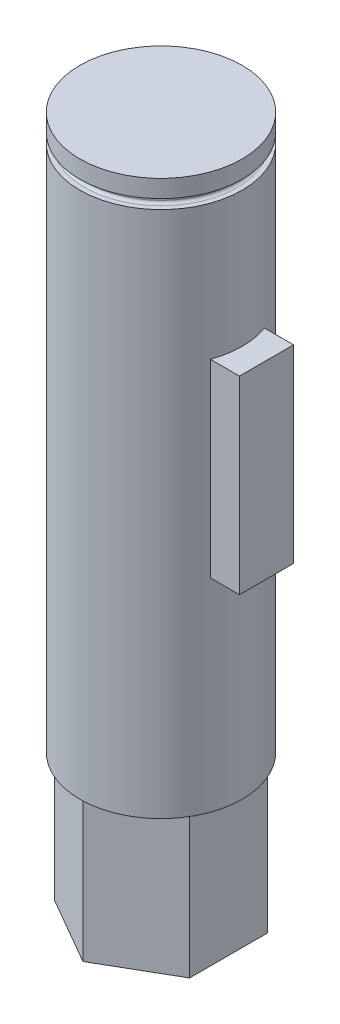
SolidWorks part; units mm, degrees
note: '?' marks a value the reader was unsure of.
ref_plane "前视基准面" through (0, 0, 0) normal (0, 0, 1) x (1, 0, 0)
ref_plane "上视基准面" through (0, 0, 0) normal (0, 1, 0) x (1, 0, 0)
ref_plane "右视基准面" through (0, 0, 0) normal (1, 0, 0) x (0, 0, -1)
sketch "Sketch1" plane through (0, 0, 0) normal (0, 1, 0) x (1, 0, 0)
  line L0 (7.8, -2) -> (7.8, 2)
  line L1 (-8.4121, 0) -> (5, 0) construction
  line L4 (7.8, 0) -> (13.7509, 0) construction
  line L5 (7.8, 2) -> (5.6569, 2)
  line L6 (7.8, -2) -> (5.6569, -2)
  arc A0 (5.6569, 2) -> (5.6569, -2) centre (0, 0) ccw
  point P8 (7.8, 0)
  dimension "D1" = 2
  dimension "D3" = 6
  dimension "D2" = 7.8
extrude "Boss-Extrude1" add sketch "Sketch1" along normal blind 14
sketch "Sketch2" plane through (0, 14, 0) normal (0, 1, 0) x (1, 0, 0)
  circle A0 centre (0, 0) radius 6
  dimension "D1" = 12
extrude "Boss-Extrude2" add sketch "Sketch2" along normal blind 12
sketch "Sketch3" plane through (0, 0, 0) normal (0, -1, 0) x (1, 0, 0)
  circle A0 centre (0, 0) radius 6
  dimension "D1" = 12
extrude "Boss-Extrude3" add sketch "Sketch3" along normal blind 15
ref_plane "Plane6" through (0, 24.35, 0) normal (0, 1, 0) x (1, 0, 0)
sketch3d "3DSketch1"
  point P0 (5.8439, 5.7238, 1.3597)
ref_axis "Axis1" through (0, 26, 0) along (0, -1, 0)?
ref_plane "Plane5" through (0, 0, 0) normal (-0.2266, 0, 0.974) x (-0.2751, -0.9593, -0.064)
sketch "Groove Sketch" plane through (1.6043, 12.1829, 0.3733) normal (-0.2266, 0, 0.974) x (-0.9343, 0.2824, -0.2174)
  line L0 (10.5354, -9.9464) -> (11.9983, -9.5157)
  line L1 (11.9983, -9.5157) -> (11.8006, -8.8442)
  line L2 (11.8006, -8.8442) -> (10.3377, -9.2749)
  line L3 (10.2023, -9.5232) -> (10.2871, -9.811)
  line L4 (15.1493, -45.6204) -> (-11.9454, 46.402) construction
  line L5 (-0.273, -14.484) -> (11.2383, -11.0946) construction
  line L6 (5.4826, -12.7893) -> (-6.0977, 26.5413) construction
  arc A0 (10.2871, -9.811) -> (10.5354, -9.9464) centre (10.4789, -9.7545) ccw
  arc A1 (10.2023, -9.5232) -> (10.3377, -9.2749) centre (10.3942, -9.4668) cw
  point P10 (10.2447, -9.6671)
  dimension "Radius" = 0.2
  dimension "ID" = 10.9
  dimension "OD" = 14.35
  dimension "Width" = 0.7
  dimension "Location" = 1.65
revolve "Retaining Ring Groove" cut sketch "Groove Sketch" angle 360 about L4 reverse direction yes
other "c-ring<1>"
sketch "Sketch5" plane through (0, -15, 0) normal (0, -1, 0) x (1, 0, 0)
  line L1 (0, 5.7735) -> (-5, 2.8868)
  line L2 (-5, 2.8868) -> (-5, -2.8868)
  line L3 (-5, -2.8868) -> (0, -5.7735)
  line L4 (0, -5.7735) -> (5, -2.8868)
  line L5 (5, -2.8868) -> (5, 2.8868)
  line L6 (5, 2.8868) -> (0, 5.7735)
  circle A0 centre (0, 0) radius 5 construction
extrude "Boss-Extrude4" add sketch "Sketch5" along normal blind 10.5
sketch "Sketch18" plane through (0, -25.5, 0) normal (0, -1, 0) x (1, 0, 0)
  point P0 (0, 0)
  point P1 (0, 0)
hole_wizard "M4 Tapped Hole1" positions "Sketch19" profile "Sketch20" tap size "M4" standard "DIN"
sketch "Sketch19" plane through (0, -25.5, 0) normal (0, -1, 0) x (-1, 0, 0)
  point P0 (0, 0)
sketch "Sketch20" plane through (0, -25.5, 0) normal (1, 0, 0) x (0, 0, -1)
  line L0 (0, 0) -> (0, 11.0914)
  line L1 (0, 11.0914) -> (1.65, 10.1)
  line L2 (1.65, 10.1) -> (1.65, 0)
  line L5 (1.65, 0) -> (0, 0)
  line L10 (0, 11.0914) -> (-1.65, 10.1) construction
  line L11 (0, -6.35) -> (0, 107.95) construction
  dimension "Tap Drill Dia." = 3.3
  dimension "Tap Drill Depth" = 10.1
  dimension "Drill Angle" = 118
cosmetic thread "Hole Thread1" parameters "D1"=8, "D2"=4
